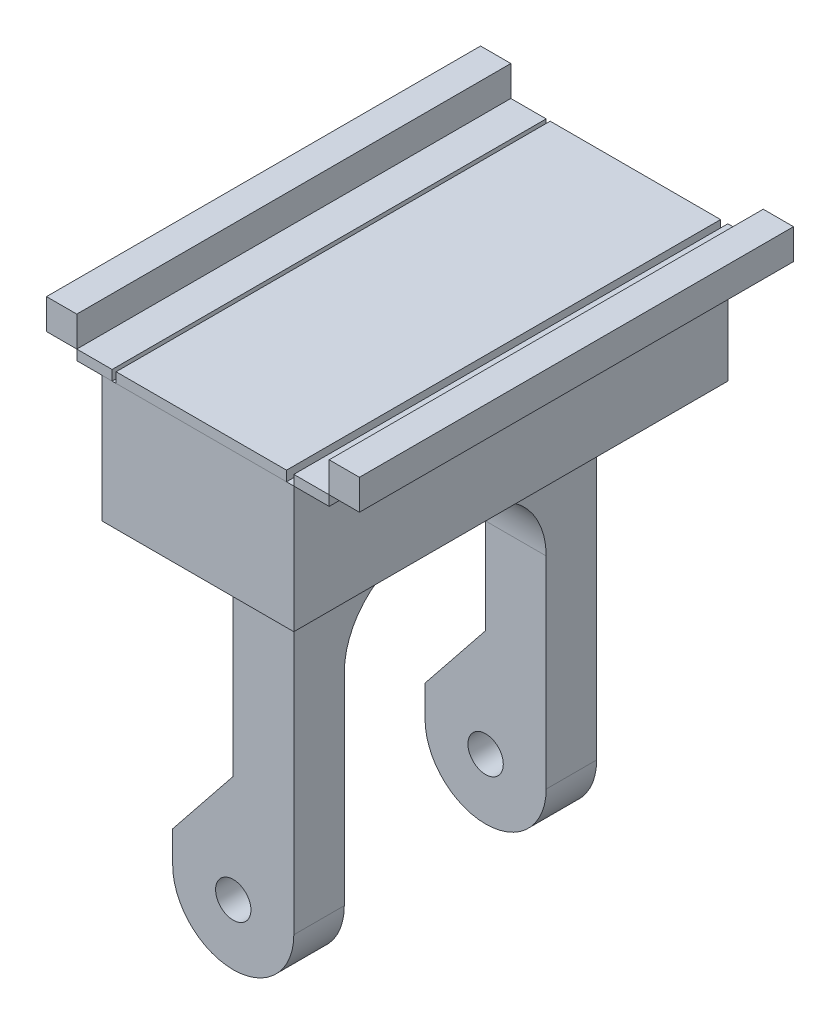
SolidWorks part; units mm, degrees
ref_plane "Front Plane" through (0, 0, 0) normal (0, 0, 1) x (1, 0, 0)
ref_plane "Top Plane" through (0, 0, 0) normal (0, 1, 0) x (1, 0, 0)
ref_plane "Right Plane" through (0, 0, 0) normal (1, 0, 0) x (0, 0, -1)
sketch "Esquisse1" plane through (0, 0, 0) normal (0, 0, 1) x (1, 0, 0)
  line L0 (-12, 0) -> (-12, 6.189)
  line L1 (-12, 6.189) -> (0, 21.1897)
  line L2 (0, 21.1897) -> (0, 60)
  line L3 (12, 0) -> (12, 60)
  line L4 (0, 60) -> (12, 60)
  circle A0 centre (0, 0) radius 3.5
  arc A1 (-12, 0) -> (12, 0) centre (0, 0) ccw
  dimension "D1" = 7
  dimension "D2" = 12
  dimension "D3" = 60
extrude "Boss.-Extru.1" add sketch "Esquisse1" along normal blind 10
sketch "Esquisse2" plane through (0, 60, 0) normal (0, 1, 0) x (1, 0, 0)
  line L0 (0, -10) -> (0, -60)
  line L1 (0, -60) -> (12, -60)
  line L2 (12, -60) -> (12, -10)
  line L4 (12, 0) -> (0, 0)
  line L5 (0, 0) -> (0, -10)
  line L6 (0, -10) -> (12, -10)
  line L7 (12, -10) -> (12, 0)
  line L8 (12, 0) -> (0, 0)
  line L9 (0, 0) -> (0, -10)
  line L11 (12, -10) -> (12, 0)
  dimension "D2" = 50
  dimension "D1" = 0
extrude "Boss.-Extru.2" add sketch "Esquisse2" along normal blind 5 separate body
ref_plane "Plan1" through (0, 0, 30) normal (0, 0, 1) x (1, 0, 0)
mirror "Symétrie2" about plane through (0, 0, 30) normal (0, 0, 1) of bodies 101
combine bodies "Combiner1" operation type add bodies to combine 103 102 101
sketch "Esquisse3" plane through (0, 60, 0) normal (0, -1, 0) x (1, 0, 0)
  line L4 (12, 10) -> (12, 50)
  line L5 (12, 50) -> (0, 50)
  line L6 (0, 50) -> (0, 10)
  line L7 (0, 10) -> (12, 10)
  line L8 (12, 10) -> (12, 50)
  line L9 (12, 50) -> (0, 50)
  line L10 (0, 50) -> (0, 10)
  line L11 (0, 10) -> (12, 10)
  dimension "D1" = 0
extrude "Boss.-Extru.3" add sketch "Esquisse3" along normal blind 5
fillet "Congé1" radius 15 2 edges at (6, 55, 10) (6, 55, 50)
sketch "Esquisse4" plane through (0, 65, 0) normal (0, 1, 0) x (1, 0, 0)
  line L8 (25, -73) -> (25, 13)
  line L9 (25, 13) -> (-13, 13)
  line L10 (-13, 13) -> (-13, -73)
  line L11 (-13, -73) -> (25, -73)
  line L12 (25, -73) -> (25, 13)
  line L13 (25, 13) -> (-13, 13)
  line L14 (-13, 13) -> (-13, -73)
  line L15 (-13, -73) -> (25, -73)
  dimension "D1" = 13
extrude "Boss.-Extru.4" add sketch "Esquisse4" along normal blind 25
sketch "Esquisse5" plane through (0, 90, 0) normal (0, 1, 0) x (1, 0, 0)
  line L8 (-8, -68) -> (20, -68)
  line L9 (20, -68) -> (20, 8)
  line L10 (20, 8) -> (-8, 8)
  line L11 (-8, 8) -> (-8, -68)
  line L12 (-8, -68) -> (20, -68)
  line L13 (20, -68) -> (20, 8)
  line L14 (20, 8) -> (-8, 8)
  line L15 (-8, 8) -> (-8, -68)
  dimension "D1" = 5
extrude "Enlèv. mat.-Extru.1" cut sketch "Esquisse5" against normal blind 25
ref_plane "Plan2" through (0, 0, 30) normal (0, 0, 1) x (1, 0, 0)
sketch "Esquisse7" plane through (0, 90, 0) normal (0, 1, 0) x (1, 0, 0)
  line L0 (25, 13) -> (25, -73)
  line L1 (25, 13) -> (32, 13)
  line L3 (32, -73) -> (25, -73)
  line L4 (32, 13) -> (32, -73)
  dimension "D1" = 7
extrude "Boss.-Extru.6" add sketch "Esquisse7" along normal blind 2 separate body
sketch "Esquisse8" plane through (0, 92, 0) normal (0, 1, 0) x (1, 0, 0)
  line L1 (32, 13) -> (38, 13)
  line L2 (32, 13) -> (32, -73)
  line L3 (32, -73) -> (38, -73)
  line L4 (38, 13) -> (38, -73)
  dimension "D1" = 6
extrude "Boss.-Extru.7" add sketch "Esquisse8" along normal blind 6 separate body
ref_plane "Plan3" through (7, 0, 0) normal (-1, 0, 0) x (0, 0, 1)
mirror "Symétrie4" about plane through (7, 0, 0) normal (-1, 0, 0) of bodies 110 111
sketch "Esquisse11" plane through (0, 90, 0) normal (0, 1, 0) x (1, 0, 0)
  line L1 (-10.2102, 13) -> (23.5525, 13)
  line L2 (-10.2102, 13) -> (-10.2102, -73)
  line L3 (-10.2102, -73) -> (23.5525, -73)
  line L4 (23.5525, 13) -> (23.5525, -73)
extrude "Boss.-Extru.10" add sketch "Esquisse11" along normal blind 2 separate body
